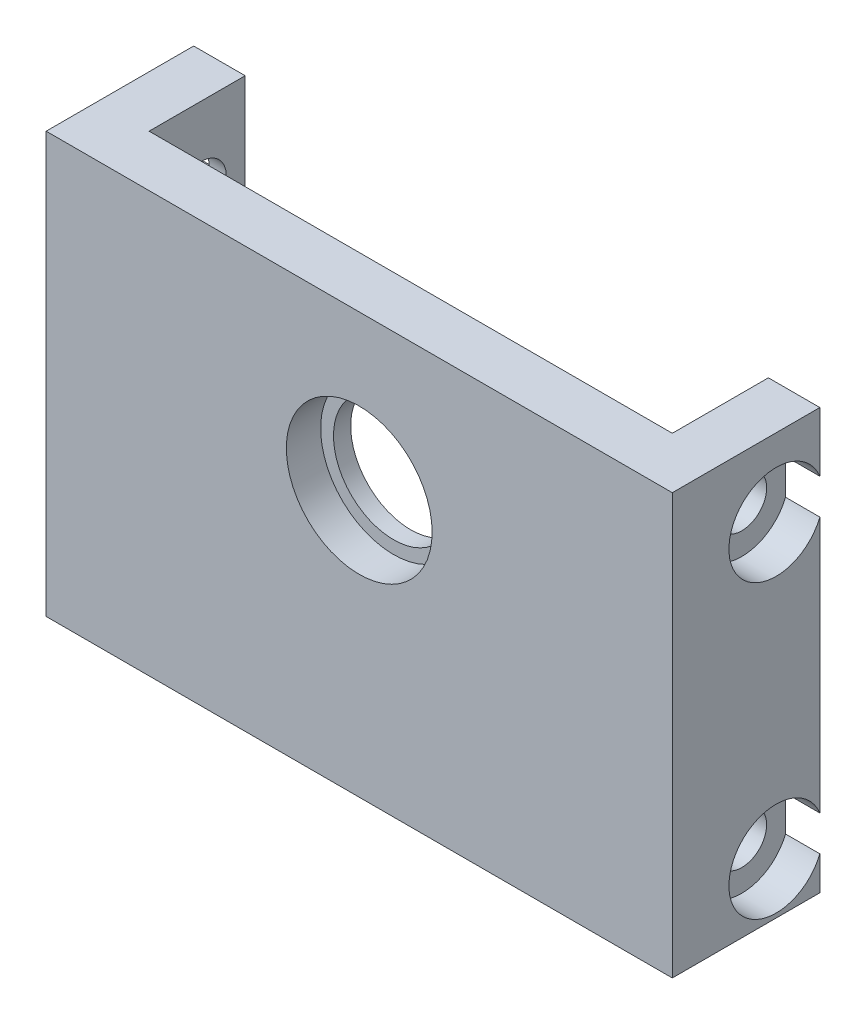
SolidWorks part; units mm, degrees
ref_plane "Plano frontal" through (0, 0, 0) normal (0, 0, 1) x (1, 0, 0)
ref_plane "Plano superior" through (0, 0, 0) normal (0, 1, 0) x (1, 0, 0)
ref_plane "Plano direito" through (0, 0, 0) normal (1, 0, 0) x (0, 0, -1)
sketch "Esboço2" plane through (0, 0, 0) normal (0, 0, 1) x (1, 0, 0)
  line L0 (2.5, -18.5) -> (4.5, -18.5) construction
  line L1 (-0.25, 3) -> (30.25, 3)
  line L2 (-0.25, 3) -> (-0.25, -21.5)
  line L3 (-0.25, -21.5) -> (30.25, -21.5)
  line L4 (30.25, 3) -> (30.25, -21.5)
  line L7 (0, -38.6) -> (0, 0) construction
  line L9 (-0.25, -1.1531) -> (0, -1.1531) construction
  line L11 (30, -1.6003) -> (30.25, -1.6003) construction
  line L12 (30, -38.6) -> (30, 0) construction
  arc A0 (18.9245, -1.4615) -> (9.4709, -3.67) centre (15, -6) ccw construction
  dimension "D1" = 9
  dimension "D2" = 0.25
  dimension "D3" = 3
extrude "Ressalto-extrusão1" add sketch "Esboço2" along normal blind 3 from offset 0.25
ref_plane "Plano1" through (15, 0, 0) normal (-1, 0, 0) x (0, 0, 1)
sketch "Esboço3" plane through (-0.25, 0, 0) normal (-1, 0, 0) x (0, 0, 1)
  line L0 (3.25, -21.5) -> (0.25, -21.5) construction
  line L1 (3.25, 3) -> (-5.35, 3)
  line L2 (3.25, 3) -> (3.25, -21.5)
  line L3 (3.25, -21.5) -> (-5.35, -21.5)
  line L4 (-5.35, 3) -> (-5.35, -21.5)
  dimension "D1" = 0.25
extrude "Ressalto-extrusão2" add sketch "Esboço3" along normal blind 3
mirror "Espelhar1" about plane through (15, 0, 0) normal (-1, 0, 0) of "Ressalto-extrusão2"
sketch "Esboço5" plane through (0, 0, 3.25) normal (0, 0, 1) x (1, 0, 0)
  circle A2 centre (15, -6) radius 4.25
  circle A3 centre (15, -6) radius 4 construction
  dimension "D1" = 0.25
extrude "Corte-extrusão1" cut sketch "Esboço5" against normal offset from surface (2 mm away) 1 up to face at (15, -9.25, 0.25)
sketch "Esboço12" plane through (0, 0, 1.25) normal (0, 0, 1) x (1, 0, 0)
  circle A2 centre (15, -6) radius 3.5
  circle A3 centre (15, -6) radius 3.25 construction
  dimension "D1" = 0.25
extrude "Corte-extrusão3" cut sketch "Esboço12" against normal through all
ref_plane "Plane1" through (15, 0, 0) normal (-1, 0, 0) x (0, 0, 1)
hole_wizard "CBORE for M2.5 SHCS1" positions "Sketch3" profile "Sketch4" counterbore size "M2.5" standard "ANSI Metric" end condition up to next
sketch "Sketch3" plane through (-3.25, 0, 0) normal (-1, 0, 0) x (0, 0, 1)
  circle A0 centre (-2.8, -1.5) radius 1.35 construction
  circle A1 centre (-2.8, -18.5) radius 1.35 construction
  point P0 (-2.8, -1.5)
  point P2 (-2.8, -18.5)
sketch "Sketch4" plane through (-3.25, -1.5, -2.8) normal (0, 1, 0) x (0, 0, 1)
  line L0 (0, 0) -> (0, 3)
  line L1 (0, 3) -> (1.45, 3)
  line L3 (1.45, 3) -> (1.45, 2)
  line L4 (1.45, 2) -> (2.75, 2)
  line L5 (2.75, 2) -> (2.75, 0)
  line L7 (2.75, 0) -> (0, 0)
  line L11 (0, -6.35) -> (0, 107.95) construction
  dimension "Thru Hole Dia." = 2.9
  dimension "Thru Hole Depth" = 3
  dimension "C'Bore Dia." = 5.5
  dimension "C'Bore Depth" = 2
mirror "Mirror1" about plane through (15, 0, 0) normal (-1, 0, 0) of "CBORE for M2.5 SHCS1"
